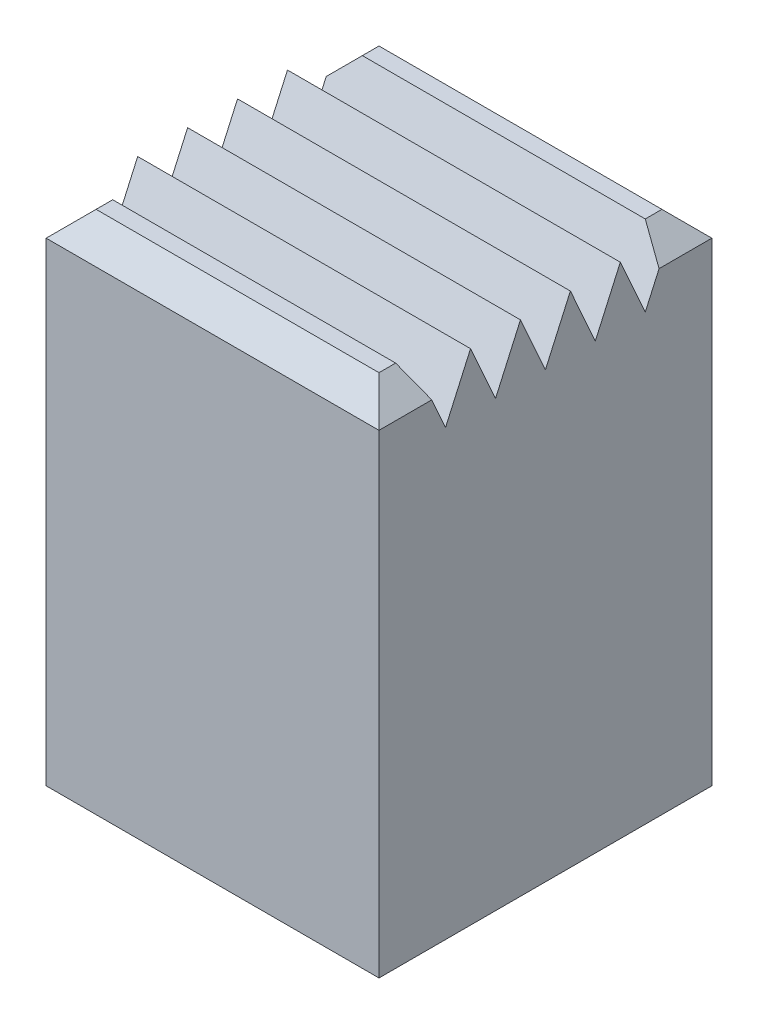
SolidWorks part; units mm, degrees
ref_plane "Front Plane" through (0, 0, 0) normal (0, 0, 1) x (1, 0, 0)
ref_plane "Top Plane" through (0, 0, 0) normal (0, 1, 0) x (1, 0, 0)
ref_plane "Right Plane" through (0, 0, 0) normal (1, 0, 0) x (0, 0, -1)
sketch "Sketch1" plane through (0, 0, 0) normal (0, 1, 0) x (1, 0, 0)
  line L1 (0, 0) -> (4, 0)
  line L2 (0, 0) -> (0, 4)
  line L3 (0, 4) -> (4, 4)
  line L4 (4, 0) -> (4, 4)
  dimension "D1" = 4
extrude "Boss-Extrude1" add sketch "Sketch1" along normal blind 6
sketch "Sketch2" plane through (0, 0, 0) normal (0, -1, 0) x (1, 0, 0)
  line L0 (2, -0.4) -> (2, 0) construction
  line L1 (0.4, -0.4) -> (3.6, -0.4)
  line L2 (0.4, -0.4) -> (0.4, -3.6)
  line L3 (0.4, -3.6) -> (3.6, -3.6)
  line L4 (3.6, -0.4) -> (3.6, -3.6)
  line L5 (0, 0) -> (4, 0) construction
  line L6 (0.4, -2) -> (0, -2) construction
  line L7 (0, -4) -> (0, 0) construction
  dimension "D1" = 3.2
extrude "Cut-Extrude1" cut sketch "Sketch2" against normal blind 4.9
sketch "Sketch3" plane through (0, 0, 0) normal (-1, 0, 0) x (0, 0, 1)
  line L0 (-3.5, 6) -> (-3.2, 5.33)
  line L1 (-4, 6) -> (0, 6) construction
  line L2 (-3.2, 5.33) -> (-2.9, 6)
  line L3 (-3.5, 6) -> (-2.9, 6)
  dimension "D1" = 0.5
  dimension "D2" = 0.6
  dimension "D3" = 0.67
extrude "Cut-Extrude2" cut sketch "Sketch3" against normal up to surface (4 mm away) contours L3 L2 L0 up to face at (4, 3, -2)
pattern_linear "LPattern1" count 5 spacing 0.6 along (0, 0, 1) of "Cut-Extrude2"
chamfer "Chamfer1" distance 0.3 angle 45 6 edges at (4, 6, -0.25) (2, 6, 0) (0, 6, -0.25) (0, 6, -3.75) (2, 6, -4) (4, 6, -3.75)
